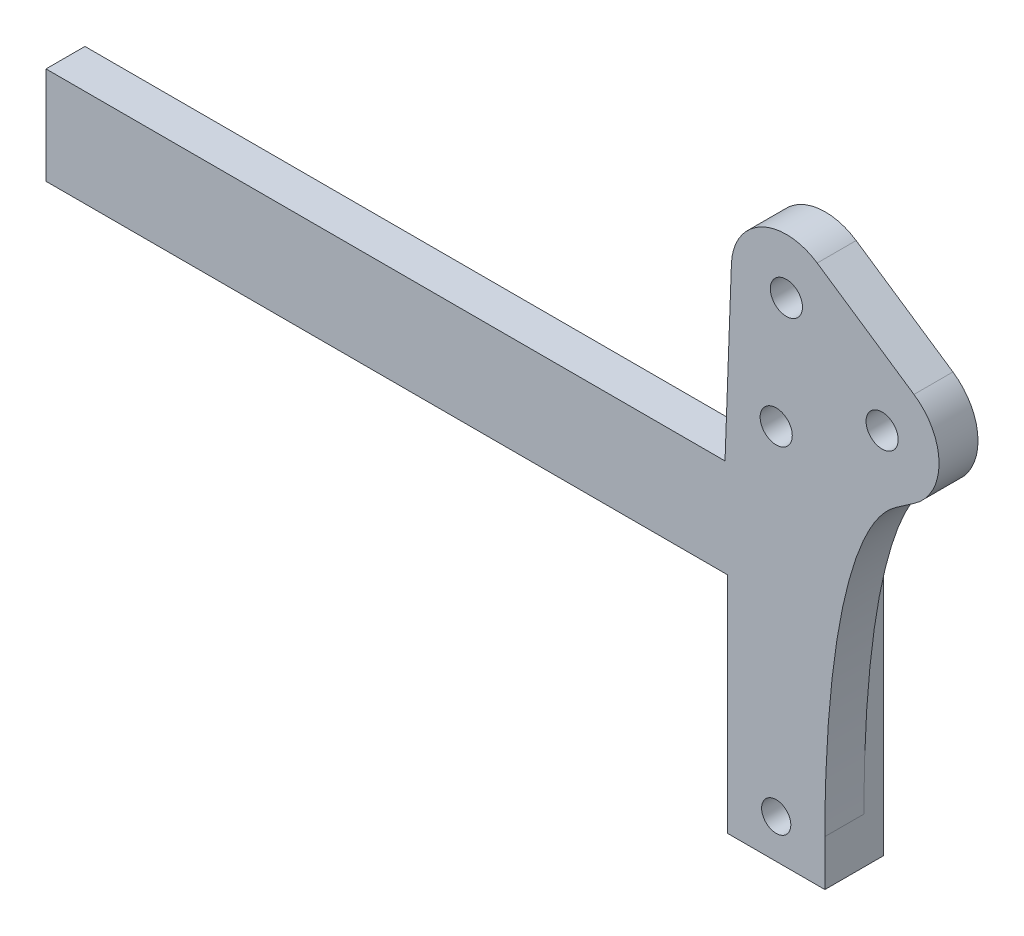
SolidWorks part; units mm, degrees
note: The reader was unsure of these and kept them because the rebuilt part matched: shared geometry of "Çizim1<3>", "Çizim4<3>", "Çizim4<6>".
ref_plane "Ön Düzlem" through (0, 0, 0) normal (0, 0, 1) x (1, 0, 0)
ref_plane "Üst Düzlem" through (0, 0, 0) normal (0, 1, 0) x (1, 0, 0)
ref_plane "Sağ Düzlem" through (0, 0, 0) normal (1, 0, 0) x (0, 0, -1)
sketch "Çizim1" plane through (0, 0, 0) normal (0, 0, 1) x (1, 0, 0)
  line L1 (-40, -5) -> (40, -5)
  line L2 (-40, -5) -> (-40, 5)
  line L3 (-40, 5) -> (40, 5)
  line L4 (40, -5) -> (40, 5)
  line L7 (40, 12) -> (30, 12)
  line L8 (40, 12) -> (40, -28)
  line L9 (40, -28) -> (30, -28)
  line L10 (30, 12) -> (30, -28)
  line L15 (0, 0) -> (40, 0) construction
  point P13 (0, 5)
  point P18 (40, 0)
  dimension "D2" = 10
  dimension "D3" = 80
  dimension "D4" = 10
  dimension "D7" = 12
  dimension "D8" = 40
extrude "Yükseklik-Ekstrüzyon1" add sketch "Çizim1" along normal blind 6
sketch "motor" plane through (0, 0, 6) normal (0, 0, 1) x (1, 0, 0)
  line L0 (30, -6) -> (40, -6) construction
  line L1 (30, 6) -> (40, 6)
  line L2 (30, 12) -> (30, 5) construction
  line L3 (30, 6) -> (30, -18)
  line L4 (30, -18) -> (40, -18)
  line L5 (40, 6) -> (40, -18)
  line L6 (40, -6) -> (40, 0) construction
  line L7 (40, 0) -> (30, 0) construction
  dimension "D1" = 6
  dimension "D2" = 24
  dimension "D3" = 10
extrude "Kes-Ekstrüzyon1" cut sketch "Çizim1<3>" along normal blind 2
sketch "Çizim1<3>" plane through (0, 0, 0) normal (0, 0, 1) x (1, 0, 0) same geometry as "Çizim1"
sketch "Çizim5" plane through (0, 0, 6) normal (0, 0, 1) x (1, 0, 0)
  line L0 (30, 6) -> (40, 6) construction
  line L1 (40, 12) -> (30, 12) construction
  line L2 (35, 10.7) -> (45.8757, 15.7714) construction
  line L3 (35, 10.7) -> (36.75, 10.7) construction
  circle A0 centre (35, 10.7) radius 1.75 construction
  circle A1 centre (45.8757, 15.7714) radius 1 construction
  point P6 (35, 12)
  dimension "D1" = 4.7
  dimension "D2" = 3.5
  dimension "D5" = 2
  dimension "D3" = 12
  dimension "D4" = 25
sketch "Çizim4" plane through (0, 0, 2) normal (0, 0, -1) x (-1, 0, 0)
  line L0 (-29.7378, 4.8749) -> (-30.3997, 22.8621)
  line L1 (-39.209, 27.3359) -> (-49.1508, 20.6187)
  line L10 (-49.1971, 10.9557) -> (-39.4569, 4.2379)
  arc A0 (-30.3997, 22.8621) -> (-39.209, 27.3359) centre (-36.0459, 22.6543) ccw
  circle A1 centre (-36.0459, 22.6543) radius 1.65
  circle A3 centre (-35, -24) radius 1.5
  circle A4 centre (-45.8757, 15.7714) radius 1.65
  arc A5 (-49.1508, 20.6187) -> (-49.1971, 10.9557) centre (-45.8757, 15.7714) ccw
  circle A6 centre (-35, 10.7) radius 1.65
  circle A11 centre (-36.0459, 22.6543) radius 1.75 construction
  circle A15 centre (-45.8757, 15.7714) radius 1.75 construction
  circle A17 centre (-35, 10.7) radius 1.75 construction
  arc A19 (-39.4569, 4.2379) -> (-29.7378, 4.8749) centre (-35, 10.7) ccw
  point P0 (-28.0692, 7.014)
  point P2 (0, 0)
  point P7 (-30, 4.7065)
  point P13 (0, 0)
  dimension "D2" = 4
  dimension "D1" = 3.3
  dimension "D4" = 4.2
  dimension "D3" = 6.2
extrude "Yükseklik-Ekstrüzyon4" add sketch "Çizim4" along direction (0, 0, 1) on the side against the normal up to surface (4 mm away)
extrude "Kes-Ekstrüzyon3" cut sketch "Çizim4<3>" against normal mid plane 10 contours A3 | A4 | A6
sketch "Çizim4<3>" plane through (0, 0, 2) normal (0, 0, -1) x (-1, 0, 0) same geometry as "Çizim4"
extrude "Kes-Ekstrüzyon5" cut sketch "Çizim4<6>" along normal blind 6
sketch "Çizim4<6>" plane through (0, 0, 2) normal (0, 0, -1) x (-1, 0, 0) same geometry as "Çizim4"
fillet "Radyus2" radius 40 1 edges at (40, 4.6125, 4) second distance 30 first distance on face at (40, -8.4325, 2.8)
